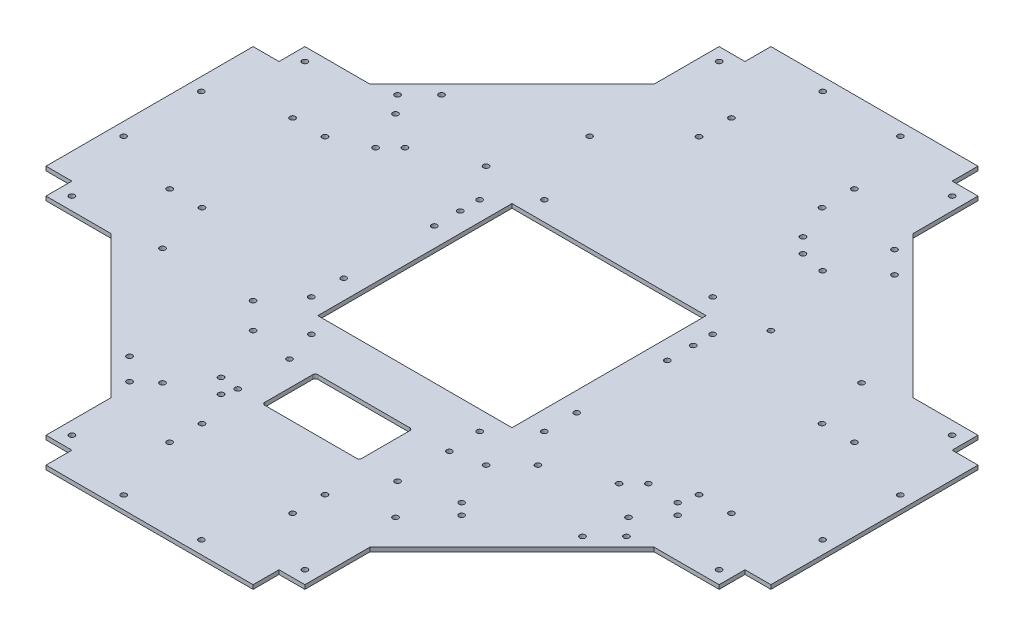
SolidWorks part; units mm, degrees
ref_plane "Front Plane" through (0, 0, 0) normal (0, 0, 1) x (1, 0, 0)
ref_plane "Top Plane" through (0, 0, 0) normal (0, 1, 0) x (1, 0, 0)
ref_plane "Right Plane" through (0, 0, 0) normal (1, 0, 0) x (0, 0, -1)
sketch "Sketch1" plane through (0, 0, 0) normal (0, 1, 0) x (1, 0, 0)
  line L0 (0, -280) -> (100, -280)
  line L1 (100, -280) -> (100, -209.6016)
  line L2 (280, -100) -> (209.6016, -100)
  line L3 (0, 0) -> (0, -280) construction
  line L4 (280, 0) -> (280, -100)
  line L5 (-280, 280) -> (280, 280) construction
  line L6 (-280, 280) -> (-280, -280) construction
  line L7 (-280, -280) -> (280, -280) construction
  line L8 (280, 280) -> (280, -280) construction
  line L9 (-280, 280) -> (280, -280) construction
  line L10 (-280, -280) -> (280, 280) construction
  line L11 (100, -209.6016) -> (209.6016, -100)
  line L12 (-280, 0) -> (-280, -100)
  line L13 (-280, -100) -> (-209.6016, -100)
  line L14 (-209.6016, -100) -> (-100, -209.6016)
  line L15 (-100, -280) -> (-100, -209.6016)
  line L16 (0, -280) -> (-100, -280)
  line L17 (0, 280) -> (-100, 280)
  line L18 (-100, 280) -> (-100, 209.6016)
  line L19 (-100, 209.6016) -> (-209.6016, 100)
  line L20 (-280, 100) -> (-209.6016, 100)
  line L21 (-280, 0) -> (-280, 100)
  line L22 (280, 0) -> (280, 100)
  line L23 (280, 100) -> (209.6016, 100)
  line L24 (209.6016, 100) -> (100, 209.6016)
  line L25 (100, 280) -> (100, 209.6016)
  line L26 (0, 280) -> (100, 280)
  line L27 (111.5258, -219.2889) -> (219.2889, -111.5258) construction
  line L28 (219.2889, -111.5258) -> (247.5732, -139.8101) construction
  line L29 (247.5732, -139.8101) -> (139.8101, -247.5732) construction
  line L30 (139.8101, -247.5732) -> (111.5258, -219.2889) construction
  line L31 (-100, -270) -> (100, -270) construction
  line L32 (-90, -280) -> (-90, 280) construction
  line L37 (-70, -70) -> (70, 70) construction
  line L38 (-70, 70) -> (70, -70) construction
  line L39 (-100, -260) -> (100, -260) construction
  line L40 (-280, 40) -> (280, 40) construction
  line L41 (0, 280) -> (0, 0) construction
  line L42 (-280, -90) -> (280, -90) construction
  line L43 (-260, -100) -> (-260, 100) construction
  line L44 (0, 0) -> (-280, 0) construction
  arc A0 (100, -280) -> (280, -100) centre (100, -100) ccw construction
  circle A1 centre (-47.5, -192) radius 2.125
  circle A2 centre (-47.5, -217) radius 2.125
  circle A3 centre (47.5, -217) radius 2.125
  circle A4 centre (47.5, -192) radius 2.125
  circle A5 centre (-192, 47.5) radius 2.125
  circle A6 centre (-217, 47.5) radius 2.125
  circle A7 centre (-192, -47.5) radius 2.125
  circle A8 centre (-217, -47.5) radius 2.125
  circle A9 centre (47.5, 192) radius 2.125
  circle A10 centre (47.5, 217) radius 2.125
  circle A11 centre (-47.5, 192) radius 2.125
  circle A12 centre (-47.5, 217) radius 2.125
  circle A13 centre (192, -47.5) radius 2.125
  circle A14 centre (217, -47.5) radius 2.125
  circle A15 centre (192, 47.5) radius 2.125
  circle A16 centre (217, 47.5) radius 2.125
  circle A17 centre (-90, -270) radius 2.125
  circle A18 centre (-30, -270) radius 2.125
  circle A19 centre (30, -270) radius 2.125
  circle A20 centre (90, -270) radius 2.125
  circle A21 centre (-270, 90) radius 2.125
  circle A22 centre (-270, 30) radius 2.125
  circle A23 centre (-270, -30) radius 2.125
  circle A24 centre (-270, -90) radius 2.125
  circle A25 centre (90, 270) radius 2.125
  circle A26 centre (30, 270) radius 2.125
  circle A27 centre (-30, 270) radius 2.125
  circle A28 centre (-90, 270) radius 2.125
  circle A29 centre (270, -90) radius 2.125
  circle A30 centre (270, -30) radius 2.125
  circle A31 centre (270, 30) radius 2.125
  circle A32 centre (270, 90) radius 2.125
  circle A33 centre (-90, -250) radius 2.125
  circle A34 centre (-90, -180) radius 2.125
  circle A35 centre (-90, -110) radius 2.125
  circle A36 centre (-90, -40) radius 2.125
  circle A37 centre (-90, 30) radius 2.125
  circle A38 centre (-90, 50) radius 2.125
  circle A39 centre (-90, 100) radius 2.125 construction
  circle A40 centre (-90, 150) radius 2.125
  circle A41 centre (-90, 200) radius 2.125 construction
  circle A42 centre (-90, 250) radius 2.125
  circle A43 centre (90, -250) radius 2.125
  circle A44 centre (90, -180) radius 2.125
  circle A45 centre (90, -110) radius 2.125
  circle A46 centre (90, -40) radius 2.125
  circle A47 centre (90, 30) radius 2.125
  circle A48 centre (90, 50) radius 2.125
  circle A49 centre (90, 100) radius 2.125 construction
  circle A50 centre (90, 150) radius 2.125
  circle A51 centre (90, 200) radius 2.125 construction
  circle A52 centre (90, 250) radius 2.125
  circle A53 centre (-250, -90) radius 2.125
  circle A54 centre (-180, -90) radius 2.125
  circle A55 centre (-110, -90) radius 2.125
  circle A56 centre (-110, 90) radius 2.125
  circle A57 centre (-180, 90) radius 2.125
  circle A58 centre (-250, 90) radius 2.125
  circle A59 centre (110, -90) radius 2.125
  circle A60 centre (180, -90) radius 2.125
  circle A61 centre (250, -90) radius 2.125
  circle A62 centre (110, 90) radius 2.125
  circle A63 centre (180, 90) radius 2.125
  circle A64 centre (250, 90) radius 2.125
  point P33 (0, 0)
  point P68 (0, 0)
  point P107 (0, 0)
  dimension "D10" = 25
  dimension "4.25" = 4.25
  dimension "D11" = 4.25
  dimension "D16" = 4.25
  dimension "D24" = 4.25
  dimension "D28" = 4.25
  dimension "D32" = 4.25
  dimension "D1" = 560
  dimension "D2" = 90
  dimension "D3" = 280
  dimension "D4" = 4
  dimension "D5" = 100
  dimension "D6" = 155
  dimension "D7" = 152.4
  dimension "D8" = 15
  dimension "D9" = 40
  dimension "D12" = 47.5
  dimension "D13" = 63
  dimension "D15" = 10
  dimension "D17" = 10
  dimension "D18" = 76.2
  dimension "D23" = 10
  dimension "D25" = 10
  dimension "D26" = 300
  dimension "D29" = 10
  dimension "D31" = 20
  dimension "D33" = 10
  dimension "D21" = 4
  dimension "D27" = 5
  dimension "D30" = 5
  dimension "D34" = 3
  dimension "D14" = 4
  dimension "D22" = 4
extrude "Boss-Extrude1" add sketch "Sketch1" along normal blind 3.175 contours L26 L17 L18 L19 L20 L21 L12 L13 L14 L15 L16 L0 L1 L11 L2 L4 L22 L23 L24 L25 region at (0, 0, -0.0137)
sketch "Sketch2" plane through (0, 3.175, 0) normal (0, 1, 0) x (1, 0, 0)
  line L0 (-90, -280) -> (-90, 280) construction
  line L1 (-75, -75) -> (75, -75)
  line L2 (-75, -75) -> (-75, 75)
  line L3 (-75, 75) -> (75, 75)
  line L4 (75, -75) -> (75, 75)
  line L5 (-75, -75) -> (75, 75) construction
  line L6 (-75, 75) -> (75, -75) construction
  line L7 (-90, -280) -> (-90, 280) construction
  line L8 (-75, 0) -> (75, 0) construction
  line L9 (0, 75) -> (0, -75) construction
  line L10 (-110, 90) -> (110, 90) construction
  line L11 (37.5, -135) -> (-37.5, -135) construction
  line L16 (-37.5, -155.5) -> (37.5, -155.5)
  line L17 (-37.5, -155.5) -> (-37.5, -114.5)
  line L18 (-37.5, -114.5) -> (37.5, -114.5)
  line L19 (37.5, -155.5) -> (37.5, -114.5)
  line L20 (-37.5, -155.5) -> (37.5, -114.5) construction
  line L21 (-37.5, -114.5) -> (37.5, -155.5) construction
  line L22 (128.2843, -167.1751) -> (98.0356, -136.9265) construction
  line L23 (146.0396, -78.7091) -> (184.862, -39.8867) construction
  line L24 (92.9289, -202.5305) -> (202.5305, -92.9289)
  line L25 (92.9289, -202.5305) -> (202.5305, -92.9289) construction
  line L26 (170.0036, -125.4558) -> (137.8448, -93.2971) construction
  circle A0 centre (66.6, -115) radius 2.125
  circle A1 centre (-90, 65) radius 2.125
  circle A2 centre (-90, -65) radius 2.125
  circle A3 centre (90, -65) radius 2.125
  circle A4 centre (90, 65) radius 2.125
  circle A5 centre (-65, 90) radius 2.125
  circle A6 centre (65, 90) radius 2.125
  circle A7 centre (65, -90) radius 2.125
  circle A8 centre (-65, -90) radius 2.125
  circle A9 centre (66.6, -155) radius 2.125
  circle A10 centre (-56.9, -115) radius 2.1
  circle A11 centre (-56.9, -155) radius 2.1
  circle A12 centre (174.9533, -120.5061) radius 2.125
  circle A13 centre (191.9239, -103.5355) radius 2.125
  circle A14 centre (153.737, -71.0118) radius 2.125
  circle A15 centre (165.0507, -59.6981) radius 2.125
  circle A16 centre (-120.5061, -174.9533) radius 2.125
  circle A17 centre (-103.5355, -191.9239) radius 2.125
  circle A18 centre (-71.0118, -153.737) radius 2.125
  circle A19 centre (-59.6981, -165.0507) radius 2.125
  circle A20 centre (-174.9533, 120.5061) radius 2.125
  circle A21 centre (-191.9239, 103.5355) radius 2.125
  circle A22 centre (-153.737, 71.0118) radius 2.125
  circle A23 centre (-165.0507, 59.6981) radius 2.125
  circle A24 centre (120.5061, 174.9533) radius 2.125
  circle A25 centre (103.5355, 191.9239) radius 2.125
  circle A26 centre (71.0118, 153.737) radius 2.125
  circle A27 centre (59.6981, 165.0507) radius 2.125
  circle A28 centre (114.1421, -153.033) radius 2.125
  circle A29 centre (105.6569, -144.5477) radius 2.1
  circle A30 centre (197.5807, -69.5944) radius 2.125
  circle A31 centre (189.0955, -61.1091) radius 2.1
  point P0 (0, 0)
  point P6 (0, -135)
  point P86 (0, 0)
  dimension "D3" = 4.25
  dimension "D5" = 4.25
  dimension "D11" = 4.25
  dimension "D14" = 4.2
  dimension "D18" = 4.25
  dimension "D20" = 4.25
  dimension "D23" = 4.25
  dimension "D25" = 4.25
  dimension "D29" = 4.25
  dimension "D31" = 4.2
  dimension "D1" = 150
  dimension "D2" = 150
  dimension "D4" = 10
  dimension "D6" = 10
  dimension "D7" = 75
  dimension "D8" = 41
  dimension "D9" = 0
  dimension "D10" = 135
  dimension "D12" = 20
  dimension "D13" = 66.6
  dimension "D15" = 19.4
  dimension "D16" = 20
  dimension "D19" = 116
  dimension "D21" = 24
  dimension "D22" = 50
  dimension "D24" = 53.85
  dimension "D26" = 16
  dimension "D28" = 50
  dimension "D30" = 20
  dimension "D32" = 12
  dimension "D33" = 59
  dimension "D17" = 10
  dimension "D27" = 4
extrude "Cut-Extrude1" cut sketch "Sketch2" against normal through all
fillet "Fillet1" radius 2 4 edges at (-37.5, 1.5875, 155.5) (37.5, 1.5875, 155.5) (37.5, 1.5875, 114.5) (-37.5, 1.5875, 114.5)
sketch "Sketch3" plane through (0, 3.175, 0) normal (0, 1, 0) x (1, 0, 0)
  line L0 (-260, 80) -> (-280, 80)
  line L1 (80, -260) -> (100, -260)
  line L2 (80, -260) -> (80, -280)
  line L3 (80, -280) -> (100, -280)
  line L4 (100, -260) -> (100, -280)
  line L5 (80, -260) -> (100, -280) construction
  line L6 (80, -280) -> (100, -260) construction
  line L7 (-80, -260) -> (-100, -260)
  line L8 (-80, -260) -> (-80, -280)
  line L9 (-80, -280) -> (-100, -280)
  line L10 (-100, -260) -> (-100, -280)
  line L11 (-80, -260) -> (-100, -280) construction
  line L12 (-80, -280) -> (-100, -260) construction
  line L13 (-260, 80) -> (-260, 100)
  line L14 (-260, 100) -> (-280, 100)
  line L15 (-280, 80) -> (-280, 100)
  line L16 (-260, -80) -> (-280, -80)
  line L17 (-260, -80) -> (-260, -100)
  line L18 (-260, -100) -> (-280, -100)
  line L19 (-280, -80) -> (-280, -100)
  line L20 (80, 260) -> (80, 280)
  line L21 (80, 260) -> (100, 260)
  line L22 (100, 260) -> (100, 280)
  line L23 (80, 280) -> (100, 280)
  line L24 (-80, 260) -> (-80, 280)
  line L25 (-80, 260) -> (-100, 260)
  line L26 (-100, 260) -> (-100, 280)
  line L27 (-80, 280) -> (-100, 280)
  line L28 (260, -80) -> (280, -80)
  line L29 (260, -80) -> (260, -100)
  line L30 (260, -100) -> (280, -100)
  line L31 (280, -80) -> (280, -100)
  line L32 (260, 80) -> (280, 80)
  line L33 (260, 80) -> (260, 100)
  line L34 (260, 100) -> (280, 100)
  line L35 (280, 80) -> (280, 100)
  point P0 (90, -270)
  point P7 (-90, -270)
  point P41 (0, 0)
extrude "Cut-Extrude2" cut sketch "Sketch3" against normal through all
